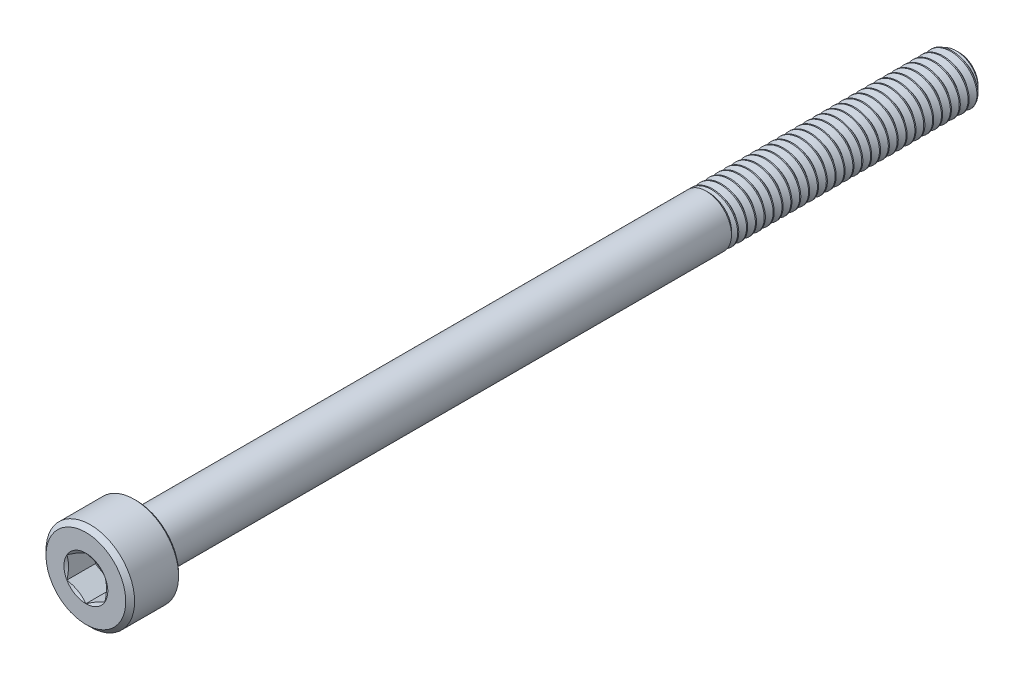
SolidWorks part; units mm, degrees
ref_plane "Front Plane" through (0, 0, 0) normal (0, 0, 1) x (1, 0, 0)
ref_plane "Top Plane" through (0, 0, 0) normal (0, 1, 0) x (1, 0, 0)
ref_plane "Right Plane" through (0, 0, 0) normal (1, 0, 0) x (0, 0, -1)
sketch "Sketch1" plane through (0, 0, 0) normal (1, 0, 0) x (0, 0, -1)
  line L0 (34.5, 0) -> (-34.5, 0) construction
  line L1 (-34.5, 0) -> (-34.5, 3.5) construction
  line L2 (-30.5, 2) -> (-30.5, 0) construction
  line L3 (33.8, 0) -> (33.8, 0.7) construction
  line L4 (14.5, 0) -> (14.5, -2) construction
  line L5 (14.5, 2) -> (34.5, 2) construction
  line L6 (34.5, -2) -> (34.5, 2) construction
  point P6 (-34.5, -1.5)
  point P9 (-34.5, 1.5)
  point P10 (14.5, 0)
  point P15 (-27.875, 0)
  point P16 (-25.9062, 0)
  point P17 (11.875, 0)
  point P18 (32.05, -2)
  point P22 (34.5, 0)
  dimension "Head Diameter" = 7
  dimension "Head Height" = 4
  dimension "Thread Size" = 4
  dimension "Length" = 65
  dimension "Thread Pitch" = 0.7
  dimension "Drive Size" = 3
  dimension "D1" = 0.7
  dimension "Min Thread Length" = 20
  dimension "D2" = 2.45
  dimension "D3" = 2.625
  dimension "D4" = 2.625
  dimension "D5" = 1.9688
sketch "Sketch2" plane through (0, 0, 0) normal (1, 0, 0) x (0, 0, -1)
  line L0 (34.5, 1.475) -> (33.975, 2)
  line L1 (-34.5, 3.5) -> (-30.5, 3.5)
  line L2 (-34.5, 3.5) -> (-34.5, 0)
  line L4 (-30.5, 3.5) -> (-30.5, 2)
  line L5 (-30.5, 2) -> (33.975, 2)
  line L8 (34.5, 1.475) -> (34.5, 0)
  line L9 (34.5, 0) -> (-34.5, 0) construction
  line L10 (34.5, 0) -> (-34.5, 0)
  dimension "D1" = 135
  dimension "D2" = 0.525
revolve "Revolve1" add sketch "Sketch2" angle 360 about L10
sketch "Sketch4" plane through (0, 0, 34.5) normal (0, 0, 1) x (1, 0, 0)
  line L1 (0, 1.7321) -> (-1.5, 0.866)
  line L2 (-1.5, 0.866) -> (-1.5, -0.866)
  line L3 (-1.5, -0.866) -> (0, -1.7321)
  line L4 (0, -1.7321) -> (1.5, -0.866)
  line L5 (1.5, -0.866) -> (1.5, 0.866)
  line L6 (1.5, 0.866) -> (0, 1.7321)
  circle A0 centre (0, 0) radius 1.5 construction
  circle A1 centre (0, 0) radius 3.5 construction
  circle A2 centre (0, 0) radius 3.5 construction
  circle A4 centre (0, 0) radius 3.5
  circle A5 centre (0, 0) radius 3.5 construction
  dimension "D1" = 3
extrude "Cut-Extrude1" cut sketch "Sketch4" against normal blind 2.25
sketch "Sketch5" plane through (0, 0, 34.5) normal (0, 0, 1) x (1, 0, 0)
  circle A0 centre (0, 0) radius 1.7321
extrude "Cut-Extrude2" cut sketch "Sketch5" against normal blind 10 draft 60
chamfer "Chamfer1" distance 0.35 angle 45 1 edges at (-3.5, 0, 34.5)
chamfer "Chamfer2" distance 0.175 angle 45 1 edges at (-3.5, 0, 30.5)
sketch "Sketch3" plane through (0, 0, -34.5) normal (0, 0, -1) x (-1, 0, 0)
  circle A0 centre (0, 0) radius 2 construction
  circle A1 centre (0, 0) radius 2
curve "Helix/Spiral1" pitch 0.7 height 20.7 turns 29.5714
sketch "Sketch8" plane through (0, 0, 30.5) normal (0, 0, -1) x (-1, 0, 0)
  circle A0 centre (0, 0) radius 2 construction
  circle A1 centre (0, 0) radius 2
sketch "Sketch7" plane through (0, 0, 0) normal (1, 0, 0) x (0, 0, -1)
  line L0 (34.4563, 2.0758) -> (34.8063, 1.4696) construction
  line L1 (34.8063, 1.4696) -> (35.1562, 2.0758) construction
  line L2 (35.1562, 2.0758) -> (34.4563, 2.0758) construction
  line L3 (34.5, 2) -> (35.1125, 2) construction
  line L4 (34.8063, 2.0758) -> (34.8063, 2) construction
  line L5 (34.8063, 2) -> (34.8063, 1.5453) construction
  line L6 (34.8063, 1.5453) -> (34.8063, 1.4696) construction
  line L7 (34.7625, 1.5453) -> (34.85, 1.5453)
  line L8 (34.4781, 2.0379) -> (35.1344, 2.0379)
  line L9 (34.85, 1.5453) -> (35.1344, 2.0379)
  line L10 (34.7625, 1.5453) -> (34.4781, 2.0379)
  point P0 (34.8063, 2.0379)
  dimension "D1" = 0.7
  dimension "D2" = 0.0875
sweep "Cut-Sweep1" cut profiles "Sketch7" path "Helix/Spiral1"
sketch "Sketch9" plane through (0, 0, 30.5) normal (0, 0, -1) x (-1, 0, 0)
  circle A0 centre (0, 0) radius 3.325 construction
  circle A1 centre (0, 0) radius 3.325
extrude "Boss-Extrude2" add sketch "Sketch9" against normal up to surface (1.75 mm away) up to face at (0, 0, 32.25)
extrude "Boss-Extrude1" add sketch "Sketch8" against normal up to surface (1.75 mm away) and the other way blind 0.7 draft 45 from vertex at 45
equation "\"D1@Sketch1\"=\"Thread Pitch@Sketch1\""
equation "\"D2@Sketch2\"=\"D1@Sketch1\"*.75"
equation "\"D4@Helix/Spiral1\"=\"Thread Pitch@Sketch1\""
equation "\"D3@Helix/Spiral1\"=\"Min Thread Length@Sketch1\"+\"Thread Pitch@Sketch1\""
equation "\"D1@Sketch4\"=\"Drive Size@Sketch1\""
equation "\"D1@Cut-Extrude1\"=\"D1@Sketch4\"*.75"
equation "\"D19\"= \"D1@Sketch4\" * .75"
equation "\"D1@Chamfer1\" = \"Head Diameter@Sketch1\" * .05"
equation "\"D1@Chamfer2\"=\"D1@Chamfer1\"/2"
equation "\"D2@Sketch7\"=\"D1@Sketch7\"/8"
equation "\"D1@Sketch7\"=\"D4@Helix/Spiral1\""
equation "\"D2@Boss-Extrude1\"=\"Thread Pitch@Sketch1\"*1"
equation "\"D2@Sketch1\"=\"Thread Pitch@Sketch1\"*3.5"
equation "\"D3@Sketch1\" = \"Head Diameter@Sketch1\" * .375"
equation "\"D4@Sketch1\"=\"D3@Sketch1\""
equation "\"D5@Sketch1\"=\"D4@Sketch1\"*.75"
